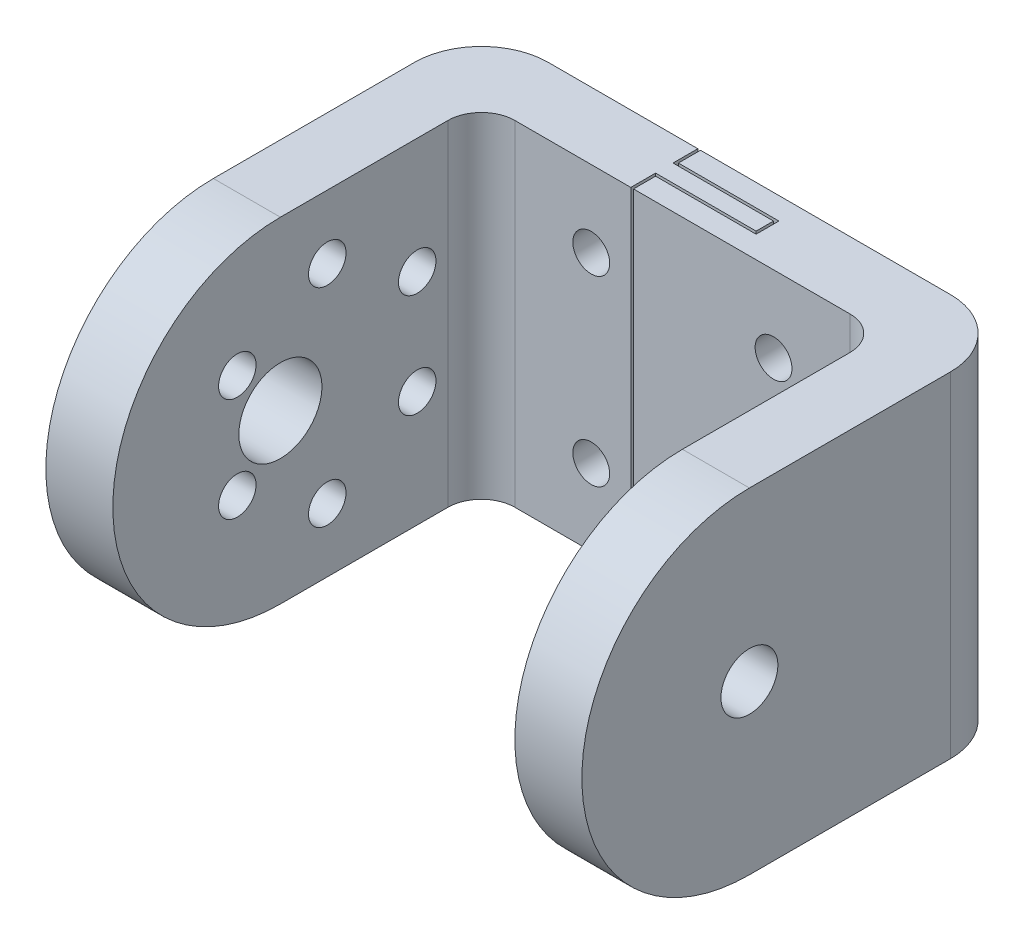
SolidWorks part; units mm, degrees
ref_plane "Front Plane" through (0, 0, 0) normal (0, 0, 1) x (1, 0, 0)
ref_plane "Top Plane" through (0, 0, 0) normal (0, 1, 0) x (1, 0, 0)
ref_plane "Right Plane" through (0, 0, 0) normal (1, 0, 0) x (0, 0, -1)
sketch "Sketch1" plane through (0, 0, 0) normal (0, 1, 0) x (1, 0, 0)
  line L1 (0, 0) -> (80, 0)
  line L2 (0, 0) -> (0, 10)
  line L3 (0, 10) -> (80, 10)
  line L4 (80, 0) -> (80, 10)
  line L5 (80, 10) -> (70, 10)
  line L6 (80, 10) -> (80, -55)
  line L7 (80, -55) -> (70, -55)
  line L8 (70, 10) -> (70, -55)
  line L9 (0, 10) -> (10, 10)
  line L10 (0, 10) -> (0, -55)
  line L11 (0, -55) -> (10, -55)
  line L12 (10, 10) -> (10, -55)
  dimension "D1" = 60
  dimension "D2" = 55
  dimension "D3" = 55
  dimension "D4" = 10
  dimension "D5" = 10
  dimension "D6" = 10
extrude "Boss-Extrude1" add sketch "Sketch1" along normal blind 50 contours L12 L1 L10 L11 | L3 L12 L1 L8 | L1 L8 L7 L6 | L3 L8 L1 L4 | L12 L3 L2 L1 region at (5, 0, -5) region at (5, 0, 27.5) region at (40, 0, -5) region at (75, 0, -5) region at (75, 0, 27.5)
sketch "Sketch2" plane through (0, 0, -10) normal (0, 0, -1) x (-1, 0, 0)
  line L0 (-40, 50) -> (-40, 0) construction
  line L1 (0, 50) -> (-80, 50) construction
  line L2 (0, 0) -> (-80, 0) construction
  line L3 (0, 25) -> (-80, 25) construction
  line L4 (0, 50) -> (0, 0) construction
  line L5 (-80, 50) -> (-80, 0) construction
  line L6 (-53.6047, 11.3953) -> (-26.3953, 11.3953) construction
  circle A0 centre (-26.3953, 38.6047) radius 2.75
  circle A1 centre (-53.6047, 38.6047) radius 2.75
  circle A2 centre (-53.6047, 11.3953) radius 2.75
  circle A3 centre (-26.3953, 11.3953) radius 2.75
  point P14 (-40, 25)
  point P24 (-40, 25)
  dimension "D2" = 5.5
  dimension "D1" = 19.24
  dimension "D3" = 4
extrude "Cut-Extrude1" cut sketch "Sketch2" against normal through all
fillet "Fillet1" 2 edges at (75, 0, 55) (75, 50, 55) type full round first side face at (40, 0, 25) second side face at (40, 50, 25) middle face at (75, 25, 55)
fillet "Fillet2" 2 edges at (5, 0, 55) (5, 50, 55) type full round first side face at (40, 0, 18.75) second side face at (40, 50, 18.75) middle face at (5, 25, 55)
sketch "Sketch3" plane through (80, 0, 0) normal (1, 0, 0) x (0, 0, -1)
  circle A0 centre (-30, 25) radius 4.25
  arc A1 (-30, 50) -> (-30, 0) centre (-30, 25) ccw construction
  dimension "D1" = 8.5
extrude "Cut-Extrude2" cut sketch "Sketch3" against normal blind 10
sketch "Sketch5" plane through (0, 0, 0) normal (-1, 0, 0) x (0, 0, 1)
  line L0 (41.4654, 25) -> (6.4654, 25) construction
  circle A0 centre (30, 25) radius 6.2
  circle A1 centre (23, 25) radius 15.5 construction
  circle A2 centre (23, 9.5) radius 1.7
  arc A8 (30, 0) -> (30, 50) centre (30, 25) ccw construction
  circle A9 centre (9.5766, 17.25) radius 1.7
  circle A10 centre (9.5766, 32.75) radius 1.7
  circle A11 centre (23, 40.5) radius 1.7
  circle A12 centre (36.4234, 32.75) radius 1.7
  circle A13 centre (36.4234, 17.25) radius 1.7
  point P18 (16.9654, 30.4369)
  point P24 (23, 25)
  dimension "D1" = 12.4
  dimension "D3" = 3.4
  dimension "D2" = 31
  dimension "D4" = 7
  dimension "D5" = 6
extrude "Cut-Extrude3" cut sketch "Sketch5" against normal blind 10
sketch "Sketch7" plane through (10, 0, 0) normal (1, 0, 0) x (0, 0, -1)
  circle A0 centre (-23, 25) radius 15.5 construction
  circle A1 centre (-23, 25) radius 15.5 construction
  circle A2 centre (-23, 9.5) radius 2.8
  circle A3 centre (-36.4234, 17.25) radius 2.8
  circle A4 centre (-36.4234, 32.75) radius 2.8
  circle A5 centre (-23, 40.5) radius 2.8
  circle A6 centre (-9.5766, 32.75) radius 2.8
  circle A7 centre (-9.5766, 17.25) radius 2.8
  point P19 (-23, 25)
  dimension "D1" = 5.6
  dimension "D2" = 6
extrude "Cut-Extrude4" cut sketch "Sketch7" against normal blind 5
fillet "Fillet3" radius 5 2 edges at (70, 25, 0) (10, 25, 0)
fillet "Fillet4" radius 10 2 edges at (0, 25, -10) (80, 25, -10)
sketch "Sketch8" plane through (0, 50, 0) normal (0, 1, 0) x (1, 0, 0)
  line L0 (32.5, 10) -> (32.5, 6.5)
  line L2 (15, 0) -> (65, 0) construction
  line L3 (10, 10) -> (70, 10) construction
  line L4 (32.5, 6.5) -> (47.5, 6.5)
  line L6 (47.5, 6.5) -> (47.5, 3.5)
  line L7 (32.5, 3.5) -> (47.5, 3.5)
  line L8 (32.5, 3.5) -> (32.5, 0)
  point P6 (40, 0)
  point P13 (40, 3.5)
  dimension "D1" = 15
  dimension "D2" = 3
  dimension "D3" = 3.5
extrude "Cut-Extrude-Thin1" cut sketch "Sketch8" against normal through all and the other way through all thin contours L0 L4 L6 L7 L8 thin type mid plane wall 0.4
